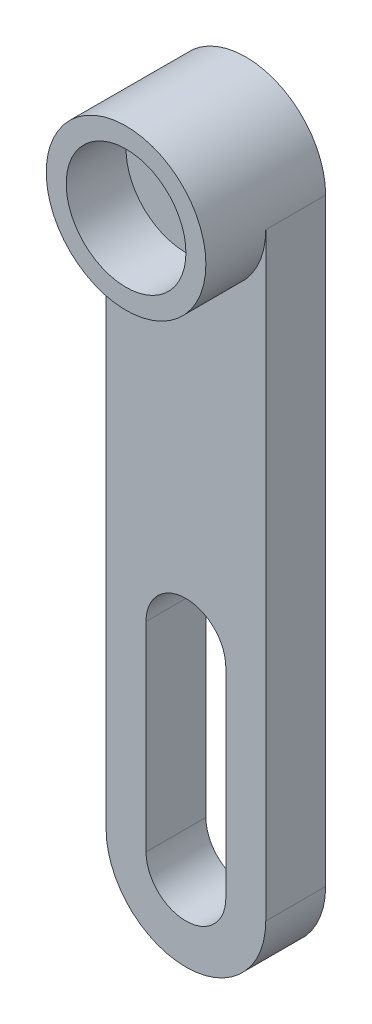
SolidWorks part; units mm, degrees
ref_plane "Front Plane" through (0, 0, 0) normal (0, 0, 1) x (1, 0, 0)
ref_plane "Top Plane" through (0, 0, 0) normal (0, 1, 0) x (1, 0, 0)
ref_plane "Right Plane" through (0, 0, 0) normal (1, 0, 0) x (0, 0, -1)
sketch "Sketch1" plane through (0, 0, 0) normal (0, 0, 1) x (1, 0, 0)
  line L0 (0, 15) -> (0, -15) construction
  line L1 (4, 15) -> (4, -15)
  line L2 (-4, 15) -> (-4, -15)
  line L3 (-2, -5) -> (-2, -15)
  line L4 (2, -15) -> (2, -5)
  arc A0 (4, 15) -> (-4, 15) centre (0, 15) ccw
  arc A1 (-4, -15) -> (4, -15) centre (0, -15) ccw
  circle A2 centre (0, 15) radius 1.25
  arc A3 (-2, -15) -> (2, -15) centre (0, -15) ccw
  arc A4 (2, -5) -> (-2, -5) centre (0, -5) ccw
  point P3 (0, 0)
  dimension "D2" = 8
  dimension "D3" = 2.5
  dimension "D4" = 4
  dimension "D5" = 4
  dimension "D1" = 30
  dimension "D6" = 10
extrude "Boss-Extrude1" add sketch "Sketch1" along normal blind 3
sketch "Sketch2" plane through (0, 0, 3) normal (0, 0, 1) x (1, 0, 0)
  circle A0 centre (0, 15) radius 4
  circle A1 centre (0, 15) radius 3
  dimension "D1" = 6
extrude "Boss-Extrude2" add sketch "Sketch2" along normal blind 3
